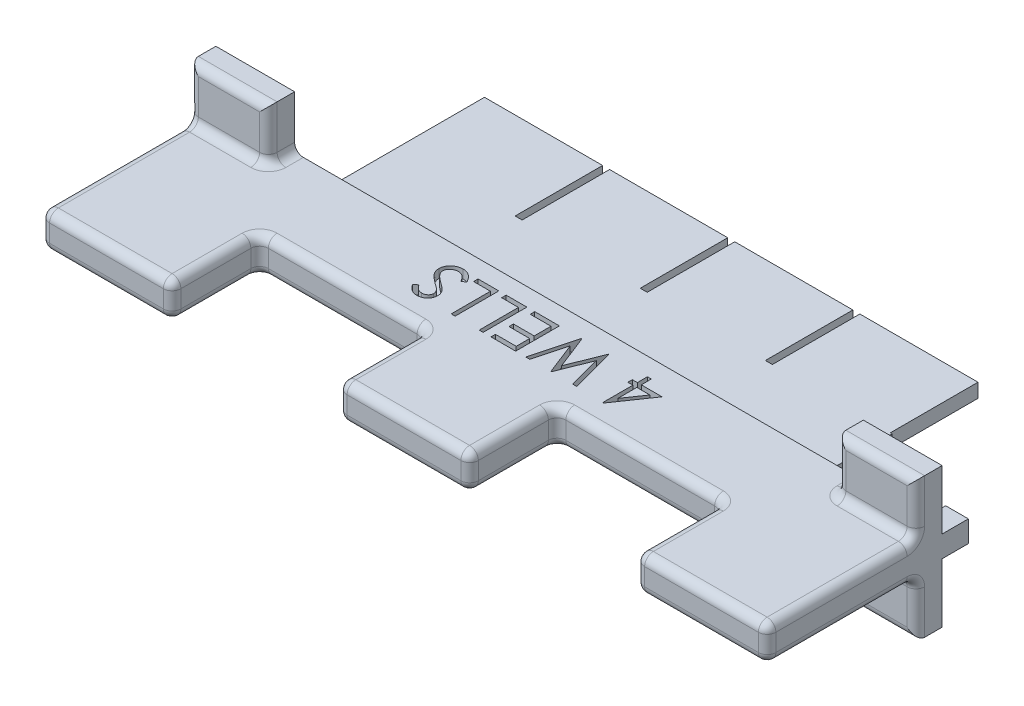
SolidWorks part; units mm, degrees
ref_plane "Front Plane" through (0, 0, 0) normal (0, 0, 1) x (1, 0, 0)
ref_plane "Top Plane" through (0, 0, 0) normal (0, 1, 0) x (1, 0, 0)
ref_plane "Right Plane" through (0, 0, 0) normal (1, 0, 0) x (0, 0, -1)
sketch "Sketch1" plane through (0, 0, 0) normal (0, 0, 1) x (1, 0, 0)
  line L1 (-41.5, 2) -> (41.5, 2)
  line L2 (-41.5, 2) -> (-41.5, -2)
  line L3 (-41.5, -2) -> (41.5, -2)
  line L4 (41.5, 2) -> (41.5, -2)
  line L5 (-41.5, 2) -> (41.5, -2) construction
  line L6 (-41.5, -2) -> (41.5, 2) construction
  point P0 (0, 0)
  dimension "D1" = 83
  dimension "D2" = 4
extrude "Boss-Extrude1" add sketch "Sketch1" along normal blind 10
sketch "Sketch2" plane through (0, 0, 10) normal (0, 0, 1) x (1, 0, 0)
  line L0 (-41.5, -2) -> (41.5, -2) construction
  line L1 (-41.5, 2) -> (-26.5, 2)
  line L2 (-41.5, 2) -> (-41.5, -2)
  line L3 (-41.5, -2) -> (-26.5, -2)
  line L4 (-26.5, 2) -> (-26.5, -2)
  line L6 (41.5, 2) -> (26.5, 2)
  line L7 (41.5, 2) -> (41.5, -2)
  line L8 (41.5, -2) -> (26.5, -2)
  line L9 (26.5, 2) -> (26.5, -2)
  line L10 (-7.5, 2) -> (7.5, 2)
  line L11 (-7.5, 2) -> (-7.5, -2)
  line L12 (-7.5, -2) -> (7.5, -2)
  line L13 (7.5, 2) -> (7.5, -2)
  line L14 (-7.5, 2) -> (7.5, -2) construction
  line L15 (-7.5, -2) -> (7.5, 2) construction
  point P12 (0, 0)
  dimension "D1" = 15
extrude "Boss-Extrude2" add sketch "Sketch2" along normal blind 10
sketch "Sketch3" plane through (0, 0, 0) normal (0, 0, -1) x (-1, 0, 0)
  line L9 (41.5, -1.225) -> (38.9, -1.225)
  line L10 (41.5, -1.225) -> (41.5, 1.225)
  line L11 (41.5, 1.225) -> (38.9, 1.225)
  line L12 (38.9, -1.225) -> (38.9, 1.225)
  line L13 (41.5, -1.225) -> (38.9, 1.225) construction
  line L14 (41.5, 1.225) -> (38.9, -1.225) construction
  line L15 (41.5, 2) -> (41.5, -2) construction
  line L16 (0, 0) -> (0, 13.9589)
  line L17 (-41.5, 1.225) -> (-38.9, -1.225) construction
  line L18 (-41.5, -1.225) -> (-38.9, 1.225) construction
  line L19 (-38.9, -1.225) -> (-38.9, 1.225)
  line L20 (-41.5, 1.225) -> (-38.9, 1.225)
  line L21 (-41.5, -1.225) -> (-41.5, 1.225)
  line L22 (-41.5, -1.225) -> (-38.9, -1.225)
  point P3 (41.5, 0)
  point P10 (40.2, 0)
  point P16 (-40.2, 0)
  line M3 (-41.5, 2) -> (-41.5, -2)
  dimension "D1" = 2.45
  dimension "D2" = 2.6
extrude "Boss-Extrude3" add sketch "Sketch3" along normal blind 3 contours L22 L19 L20 M3 | L12 L11 L10 L9 region at (40.2, 0, 0)
sketch "Sketch4" plane through (0, 0, 0) normal (0, 0, -1) x (-1, 0, 0)
  line L0 (-41.5, -2) -> (-41.5, -1.225) construction
  line L1 (28.3, -0.8) -> (-28.3, -0.8)
  line L2 (28.3, -0.8) -> (28.3, 0.8)
  line L3 (28.3, 0.8) -> (-28.3, 0.8)
  line L4 (-28.3, -0.8) -> (-28.3, 0.8)
  line L5 (28.3, -0.8) -> (-28.3, 0.8) construction
  line L6 (28.3, 0.8) -> (-28.3, -0.8) construction
  point P0 (0, 0)
  dimension "D1" = 1.6
  dimension "D2" = 13.2
extrude "Boss-Extrude4" add sketch "Sketch4" along normal blind 7.5
sketch "Sketch5" plane through (0, 0, -7.5) normal (0, 0, -1) x (-1, 0, 0)
  line L0 (28.3, 0.8) -> (-28.3, 0.8) construction
  line L1 (28.3, -0.8) -> (14.8, -0.8)
  line L2 (28.3, -0.8) -> (28.3, 0.8)
  line L3 (28.3, 0.8) -> (14.8, 0.8)
  line L4 (14.8, -0.8) -> (14.8, 0.8)
  line L29 (14, -0.8) -> (0.5, -0.8)
  line L30 (14, -0.8) -> (14, 0.8)
  line L31 (14, 0.8) -> (0.5, 0.8)
  line L32 (0.5, -0.8) -> (0.5, 0.8)
  line L33 (-0.3, -0.8) -> (-13.8, -0.8)
  line L34 (-0.3, -0.8) -> (-0.3, 0.8)
  line L35 (-0.3, 0.8) -> (-13.8, 0.8)
  line L36 (-13.8, -0.8) -> (-13.8, 0.8)
  line L37 (-14.6, -0.8) -> (-28.1, -0.8)
  line L38 (-14.6, -0.8) -> (-14.6, 0.8)
  line L39 (-14.6, 0.8) -> (-28.1, 0.8)
  line L40 (-28.1, -0.8) -> (-28.1, 0.8)
  dimension "D2" = 13.5
  dimension "D1" = 4
extrude "Boss-Extrude5" add sketch "Sketch5" along normal blind 10
sketch "Sketch6" plane through (0, 0, 0) normal (0, 0, -1) x (-1, 0, 0)
  line L1 (41.5, -2) -> (32.5, -2)
  line L2 (41.5, -2) -> (41.5, -8)
  line L3 (41.5, -8) -> (32.5, -8)
  line L4 (32.5, -2) -> (32.5, -8)
  line L5 (41.5, 2) -> (32.5, 2)
  line L6 (41.5, 2) -> (41.5, 8)
  line L7 (41.5, 8) -> (32.5, 8)
  line L8 (32.5, 2) -> (32.5, 8)
  line L9 (-41.5, -2) -> (-32.5, -2)
  line L10 (-41.5, -2) -> (-41.5, -8)
  line L11 (-41.5, -8) -> (-32.5, -8)
  line L12 (-32.5, -2) -> (-32.5, -8)
  line L13 (-41.5, 2) -> (-32.5, 2)
  line L14 (-41.5, 2) -> (-41.5, 8)
  line L15 (-41.5, 8) -> (-32.5, 8)
  line L16 (-32.5, 2) -> (-32.5, 8)
  dimension "D1" = 6
  dimension "D2" = 9
extrude "Boss-Extrude6" add sketch "Sketch6" against normal blind 3
fillet "Fillet1" radius 1 52 edges at (-41.5, -2, 11.5) (-32.5, -2, 1.5) (-37, -2, 3) (-32.5, -5, 3) (-37, -8, 3) (-41.5, -5, 3) (-26.5, 0, 20) (-34, -2, 20) (-41.5, 0, 20) (-34, 2, 20) (32.5, -2, 1.5) (41.5, -2, 11.5) (41.5, 2, 11.5) (32.5, 2, 1.5) (-32.5, 2, 1.5) (-41.5, 2, 11.5) (37, -8, 3) (32.5, -5, 3) (37, -2, 3) (41.5, -5, 3) (34, -2, 20) (26.5, 0, 20) (34, 2, 20) (41.5, 0, 20) (37, 2, 3) (32.5, 5, 3) (37, 8, 3) (41.5, 5, 3) (0, -2, 20) (-7.5, 0, 20) (0, 2, 20) (7.5, 0, 20) (-37, 8, 3) (-32.5, 5, 3) (-37, 2, 3) (-41.5, 5, 3) (26.5, 2, 15) (26.5, -2, 15) (26.5, 0, 10) (17, -2, 10) (17, 2, 10) (7.5, -2, 15) (7.5, 2, 15) (7.5, 0, 10) (-7.5, 2, 15) (-7.5, -2, 15) (-26.5, -2, 15) (-26.5, 2, 15) (-26.5, 0, 10) (-17, 2, 10) (-7.5, 0, 10) (-17, -2, 10)
ref_plane "Plane1" through (0, 0, 0) normal (0, 1, 0) x (1, 0, 0)
sketch "Sketch7" plane through (0, 2, 0) normal (0, 1, 0) x (1, 0, 0)
  line L0 (30.9142, -2.045) -> (-30.9142, -2.045)
  line L1 (31.5, 0) -> (-31.5, 0) construction
  point P2 (0, -2.045)
  point P5 (0, 0)
sketch "Sketch8" plane through (0, 2, 0) normal (0, 1, 0) x (1, 0, 0)
  text T0 "4 WELLS" font "Century Gothic" height 5
extrude "Cut-Extrude1" cut sketch "Sketch8" against normal blind 1
